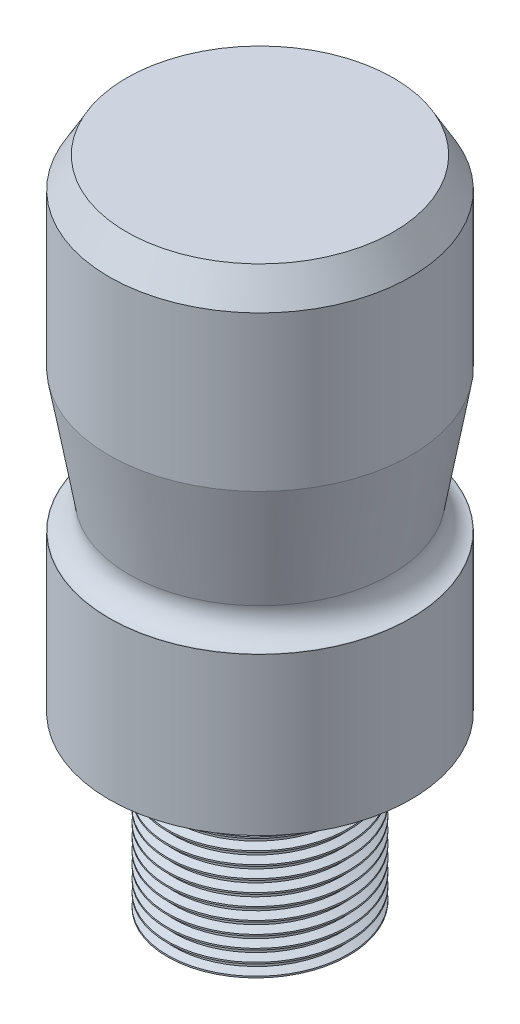
SolidWorks part; units mm, degrees
ref_plane "Front Plane" through (0, 0, 0) normal (0, 0, 1) x (1, 0, 0)
ref_plane "Top Plane" through (0, 0, 0) normal (0, 1, 0) x (1, 0, 0)
ref_plane "Right Plane" through (0, 0, 0) normal (1, 0, 0) x (0, 0, -1)
sketch "Sketch1" plane through (0, 0, 0) normal (0, 0, 1) x (1, 0, 0)
  line L0 (0, -55.2685) -> (0, 52.7315) construction
  line L1 (0, 52.7315) -> (22.1132, 52.7315)
  line L2 (22.1132, 52.7315) -> (25, 47.7315)
  line L3 (25, 47.7315) -> (25, 22.1219)
  line L4 (25, 22.1219) -> (21.6946, 3.376)
  line L5 (24.9392, -1.2578) -> (25, -1.2685)
  line L6 (25, -1.2685) -> (25, -27.2685)
  line L7 (25, -27.2685) -> (12.5, -27.2685)
  line L8 (12.5, -27.2685) -> (12.5, -30.2685)
  line L9 (12.5, -30.2685) -> (15, -30.2685)
  line L10 (15, -30.2685) -> (15, -55.2685)
  line L11 (15, -55.2685) -> (0, -55.2685)
  line L12 (0, 52.7315) -> (0, -55.2685)
  arc A0 (21.6946, 3.376) -> (24.9392, -1.2578) centre (25.6338, 2.6814) ccw
  point P15 (21, -0.5632)
  point P17 (21, -0.5632)
  dimension "D13" = 90
  dimension "D14" = 4
  dimension "D1" = 30
  dimension "D2" = 25
  dimension "D3" = 50
  dimension "D4" = 42
  dimension "D5" = 50
  dimension "D6" = 30
  dimension "D7" = 5
  dimension "D8" = 10
  dimension "D9" = 26
  dimension "D10" = 25
  dimension "D11" = 3
  dimension "D12" = 108
revolve "Revolve1" add sketch "Sketch1" angle 360 about L0
cosmetic thread "Cosmetic Thread1" parameters "D2"=27.797
thread "Thread2" pitch 2 method cut profile "Thread Profile2" start angle 0, offset 5, length 31, pitch 2, diameter 30
ref_plane "Plane2" through (15, -60.2685, 0) normal (0, 0, 1) x (1, 0, 0)
sketch "Thread Profile2" plane through (15, -60.2685, 0) normal (0, 0, 1) x (1, 0, 0)
  line L0 (0, 0) -> (0, 2) construction
  line L11 (0, 0) -> (0, 1.75)
  line L12 (0, 1.75) -> (-1.0825, 1.125)
  line L13 (-1.0825, 1.125) -> (-1.0825, 0.625)
  line L15 (-1.0825, 0.625) -> (0, 0)
  line L17 (-1.0825, 0.875) -> (0, 0.875) construction
  point P2 (0, 0)
  dimension "Pitch" = 2
  dimension "Profile_Angle" = 60
  dimension "Profile_Land" = 0.5
  dimension "Profile_Height" = 1.0825
